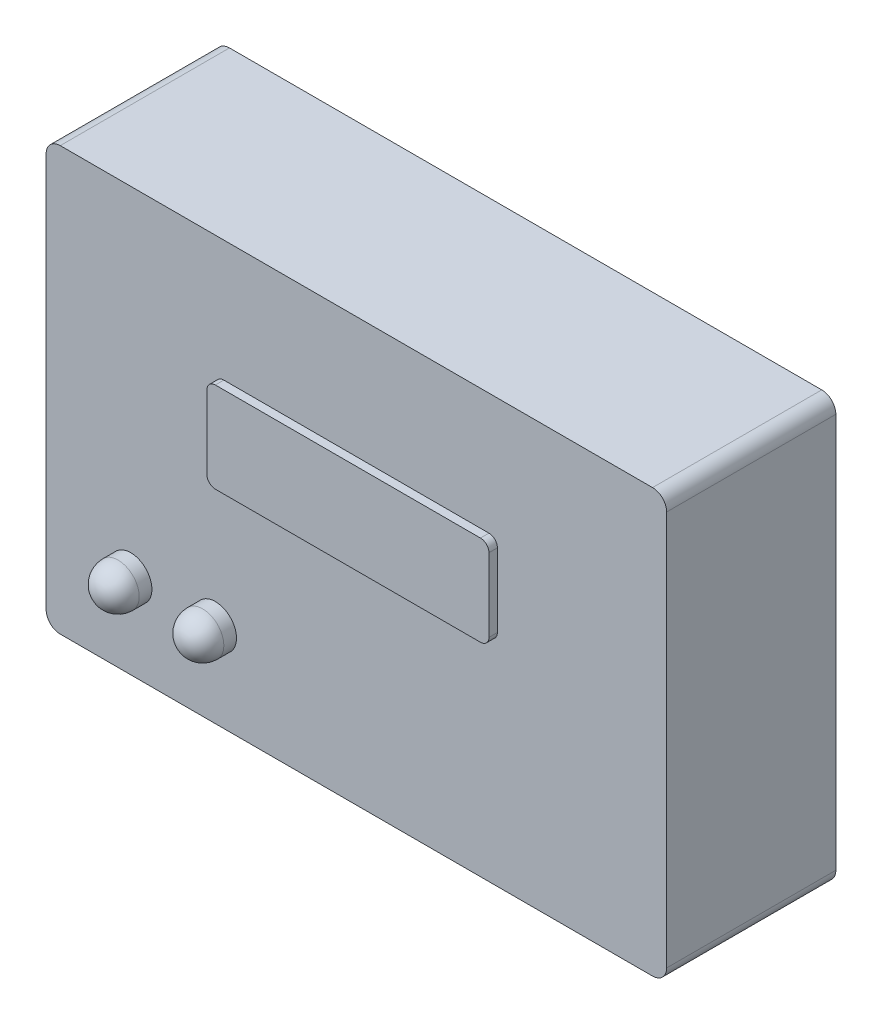
SolidWorks part; units mm, degrees
ref_plane "Front Plane" through (0, 0, 0) normal (0, 0, 1) x (1, 0, 0)
ref_plane "Top Plane" through (0, 0, 0) normal (0, 1, 0) x (1, 0, 0)
ref_plane "Right Plane" through (0, 0, 0) normal (1, 0, 0) x (0, 0, -1)
sketch "Sketch1" plane through (0, 0, 0) normal (0, 0, 1) x (1, 0, 0)
  line L1 (-105, -75) -> (105, -75)
  line L2 (-110, -70) -> (-110, 70)
  line L3 (-105, 75) -> (105, 75)
  line L4 (110, -70) -> (110, 70)
  line L5 (-110, -75) -> (110, 75) construction
  line L6 (-110, 75) -> (110, -75) construction
  arc A0 (105, -75) -> (110, -70) centre (105, -70) ccw
  arc A1 (-105, -75) -> (-110, -70) centre (-105, -70) cw
  arc A2 (105, 75) -> (110, 70) centre (105, 70) cw
  arc A3 (-110, 70) -> (-105, 75) centre (-105, 70) cw
  point P0 (0, 0)
  dimension "D3" = 5
  dimension "D1" = 150
  dimension "D2" = 220
extrude "Boss-Extrude1" add sketch "Sketch1" along normal mid plane 60
sketch "Sketch2" plane through (0, 0, -30) normal (0, 0, -1) x (-1, 0, 0)
  line L8 (-105, -73) -> (105, -73)
  line L9 (108, -70) -> (108, 70)
  line L10 (105, 73) -> (-105, 73)
  line L11 (-108, 70) -> (-108, -70)
  line L12 (-105, -73) -> (105, -73)
  line L13 (108, -70) -> (108, 70)
  line L14 (105, 73) -> (-105, 73)
  line L15 (-108, 70) -> (-108, -70)
  arc A8 (-108, -70) -> (-105, -73) centre (-105, -70) ccw
  arc A9 (105, -73) -> (108, -70) centre (105, -70) ccw
  arc A10 (108, 70) -> (105, 73) centre (105, 70) ccw
  arc A11 (-105, 73) -> (-108, 70) centre (-105, 70) ccw
  arc A12 (-108, -70) -> (-105, -73) centre (-105, -70) ccw
  arc A13 (105, -73) -> (108, -70) centre (105, -70) ccw
  arc A14 (108, 70) -> (105, 73) centre (105, 70) ccw
  arc A15 (-105, 73) -> (-108, 70) centre (-105, 70) ccw
  dimension "D1" = 2
extrude "Cut-Extrude1" cut sketch "Sketch2" against normal blind 20
sketch "Sketch3" plane through (0, 0, -10) normal (0, 0, -1) x (-1, 0, 0)
  circle A0 centre (25, 0) radius 2.5
  circle A1 centre (-25, 0) radius 5
  circle A2 centre (-25, 0) radius 7
  point P5 (0, 0)
  dimension "D1" = 5
  dimension "D2" = 10
  dimension "D3" = 14
  dimension "D4" = 25
  dimension "D5" = 25
extrude "Boss-Extrude2" add sketch "Sketch3" along normal blind 3 separate body contours A0
extrude "Boss-Extrude3" add sketch "Sketch3<3>" along normal blind 5 separate body contours A1 region at (25, 0, -10)
sketch "Sketch3<3>" plane through (0, 0, -10) normal (0, 0, -1) x (-1, 0, 0) same geometry as "Sketch3"
extrude "Boss-Extrude4" add sketch "Sketch3<4>" along normal blind 6 separate body contours A2 A1 region at (31.802, 0, -10)
sketch "Sketch3<4>" plane through (0, 0, -10) normal (0, 0, -1) x (-1, 0, 0) same geometry as "Sketch3"
sketch "Sketch4" plane through (0, 0, 30) normal (0, 0, 1) x (1, 0, 0)
  line L1 (-47, 32) -> (47, 32)
  line L2 (-50, 29) -> (-50, 3)
  line L3 (-47, 0) -> (47, 0)
  line L4 (50, 29) -> (50, 3)
  arc A0 (47, 0) -> (50, 3) centre (47, 3) ccw
  arc A1 (-50, 3) -> (-47, 0) centre (-47, 3) ccw
  arc A2 (47, 32) -> (50, 29) centre (47, 29) cw
  arc A3 (-47, 32) -> (-50, 29) centre (-47, 29) ccw
  point P7 (50, 0)
  point P12 (50, 32)
  point P15 (-50, 32)
  dimension "D3" = 3
  dimension "D1" = 32
  dimension "D2" = 100
extrude "Boss-Extrude5" add sketch "Sketch4" along normal blind 3 separate body
sketch "Sketch5" plane through (0, 0, 30) normal (0, 0, 1) x (1, 0, 0)
  line L0 (-110, 70) -> (-110, -70) construction
  line L1 (-105, -75) -> (105, -75) construction
  circle A0 centre (-80, -45) radius 7.5
  circle A1 centre (-50, -45) radius 7.5
  point P4 (0, 0)
  point P11 (-57.3351, -39.5531)
  dimension "D1" = 15
  dimension "D2" = 15
  dimension "D3" = 30
  dimension "D4" = 30
  dimension "D5" = 30
extrude "Boss-Extrude6" add sketch "Sketch5" along normal blind 12 separate body
fillet "Fillet2" radius 7.5 1 edges at (-72.5, -45, 42)
fillet "Fillet3" radius 7.5 1 edges at (-42.5, -45, 42)
